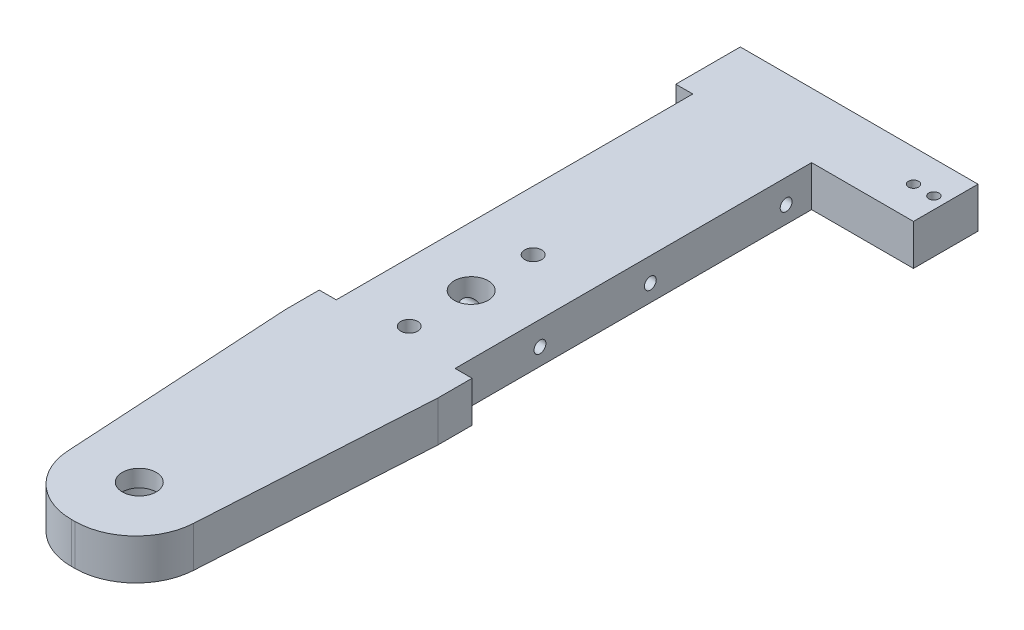
SolidWorks part; units mm, degrees
ref_plane "Front Plane" through (0, 0, 0) normal (0, 0, 1) x (1, 0, 0)
ref_plane "Top Plane" through (0, 0, 0) normal (0, 1, 0) x (1, 0, 0)
ref_plane "Right Plane" through (0, 0, 0) normal (1, 0, 0) x (0, 0, -1)
sketch "Sketch1" plane through (0, 0, 0) normal (0, 1, 0) x (1, 0, 0)
  line L1 (-22.5, 125) -> (22.5, 125)
  line L2 (-22.5, 125) -> (-22.5, -125)
  line L3 (-22.5, -125) -> (22.5, -125)
  line L4 (22.5, 125) -> (22.5, -125)
  line L5 (-22.5, 125) -> (22.5, -125) construction
  line L6 (-22.5, -125) -> (22.5, 125) construction
  point P0 (0, 0)
  dimension "D1" = 250
  dimension "D2" = 45
extrude "Boss-Extrude1" add sketch "Sketch1" along normal blind 12
sketch "Sketch2" plane through (0, 12, 0) normal (0, 1, 0) x (1, 0, 0)
  line L0 (22.5, 125) -> (22.5, 113) construction
  line L1 (22.5, -125) -> (22.5, 125) construction
  line L2 (0, -6.6) -> (0, 6.6) construction
  line L3 (22.5, 113) -> (17.5, 113)
  line L4 (22.5, 113) -> (22.5, 8)
  line L5 (22.5, 8) -> (17.5, 8)
  line L6 (17.5, 113) -> (17.5, 8)
  line L7 (-22.5, 8) -> (-17.5, 8)
  line L8 (-17.5, 113) -> (-17.5, 8)
  line L9 (-22.5, 113) -> (-17.5, 113)
  line L10 (-22.5, 113) -> (-22.5, 8)
  line L11 (0, 125) -> (0, 128) construction
  line L12 (-22.5, -125) -> (22.5, -125)
  line L13 (-22.5, -125) -> (-22.5, -110)
  line L14 (-22.5, -110) -> (22.5, -110)
  line L15 (22.5, -125) -> (22.5, -110)
  line L16 (22.5, 125) -> (-22.5, 125) construction
  line L17 (0, 128) -> (0, 48.5) construction
  line L18 (0, 48.5) -> (0, 12) construction
  line L19 (0, 12) -> (0, -49.25) construction
  line L20 (0, -49.25) -> (0, -85.75) construction
  circle A4 centre (0, 12) radius 2.5
  circle A5 centre (0, 30.25) radius 5
  circle A6 centre (0, 48.5) radius 2.5
  circle A8 centre (0, -67.5) radius 5
  dimension "D2" = 105
  dimension "D7" = 36.5
  dimension "D8" = 61.25
  dimension "D6" = 79.5
  dimension "D10" = 5
  dimension "D11" = 10
  dimension "D12" = 5
  dimension "D15" = 10
  dimension "D1" = 12
  dimension "D3" = 5
  dimension "D4" = 15
  dimension "D5" = 3
  dimension "D13" = 36.5
extrude "Cut-Extrude1" cut sketch "Sketch2" against normal blind 12
sketch "Sketch3" plane through (17.5, 0, 0) normal (1, 0, 0) x (0, 0, -1)
  line L0 (113, 12) -> (113, 5) construction
  line L2 (113, 0) -> (113, 12) construction
  line L3 (113, 5) -> (105.5, 5) construction
  line L4 (105.5, 5) -> (65.5, 5) construction
  line L5 (65.5, 5) -> (33, 5) construction
  circle A2 centre (33, 5) radius 1.75
  circle A3 centre (65.5, 5) radius 1.75
  circle A4 centre (105.5, 5) radius 1.75
  dimension "D3" = 40
  dimension "D4" = 32.5
  dimension "D5" = 3.5
  dimension "D6" = 3.5
  dimension "D7" = 3.5
  dimension "D1" = 7
  dimension "D2" = 7.5
extrude "Cut-Extrude2" cut sketch "Sketch3" against normal blind 35
sketch "Sketch4" plane through (0, 12, 0) normal (0, 1, 0) x (1, 0, 0)
  line L9 (22.5, 125) -> (47.5, 125)
  line L10 (22.5, 125) -> (22.5, 113)
  line L11 (22.5, 113) -> (47.5, 113)
  line L12 (47.5, 125) -> (47.5, 113)
  dimension "D1" = 25
extrude "Boss-Extrude2" add sketch "Sketch4" against normal blind 12
sketch "Sketch5" plane through (0, 12, 0) normal (0, 1, 0) x (1, 0, 0)
  line L10 (22.5, -110) -> (22.5, 8) construction
  line L11 (-22.5, -110) -> (22.5, -110)
  line L12 (-22.5, -110) -> (-22.5, -87)
  line L13 (-22.5, -87) -> (22.5, -87)
  line L14 (22.5, -110) -> (22.5, -87)
  dimension "D2" = 23
extrude "Cut-Extrude3" cut sketch "Sketch5" against normal blind 20
sketch "Sketch6" plane through (0, 12, 0) normal (0, 1, 0) x (1, 0, 0)
  line L1 (-22.5, 125) -> (47.5, 125)
  line L2 (-22.5, 125) -> (-22.5, 132)
  line L3 (-22.5, 132) -> (47.5, 132)
  line L4 (47.5, 125) -> (47.5, 132)
  dimension "D1" = 7
extrude "Boss-Extrude3" add sketch "Sketch6" against normal up to surface (12 mm away) up to face at (0, 0, -25.25)
sketch "Sketch7" plane through (0, 12, 0) normal (0, 1, 0) x (1, 0, 0)
  line L0 (47.5, 132) -> (41, 132) construction
  line L1 (41, 132) -> (41, 122.5) construction
  line L2 (41, 122.5) -> (38, 122.5) construction
  circle A0 centre (38, 122.5) radius 1.5
  circle A1 centre (44, 122.5) radius 1.5
  dimension "D2" = 3
  dimension "D3" = 3
  dimension "D1" = 6.5
extrude "Cut-Extrude4" cut sketch "Sketch7" against normal up to surface (12 mm away) up to face at (0, 0, -25.25)
sketch "Sketch8" plane through (0, 12, 0) normal (0, 1, 0) x (1, 0, 0)
  line L0 (-22.5, 8) -> (-22.5, -2) construction
  line L1 (-22.5, 8) -> (-22.5, -87) construction
  line L2 (-22.5, -2) -> (-22.5, -87)
  line L3 (-22.5, -87) -> (-17.5, -87)
  line L4 (22.5, -87) -> (-22.5, -87) construction
  line L5 (-17.5, -87) -> (-22.5, -2)
  line L6 (0, -6.6) -> (0, 6.6) construction
  line L7 (17.5, -87) -> (22.5, -2)
  line L8 (22.5, -87) -> (17.5, -87)
  line L9 (22.5, -2) -> (22.5, -87)
  dimension "D1" = 10
  dimension "D2" = 5
extrude "Cut-Extrude5" cut sketch "Sketch8" against normal blind 20
fillet "Fillet1" radius 18 2 edges at (17.5, 6, 87) (-17.5, 6, 87)
sketch "Sketch9" plane through (0, 0, 0) normal (0, -1, 0) x (1, 0, 0)
  circle A0 centre (0, 67.5) radius 11
  dimension "D1" = 22
extrude "Cut-Extrude6" cut sketch "Sketch9" against normal blind 7
